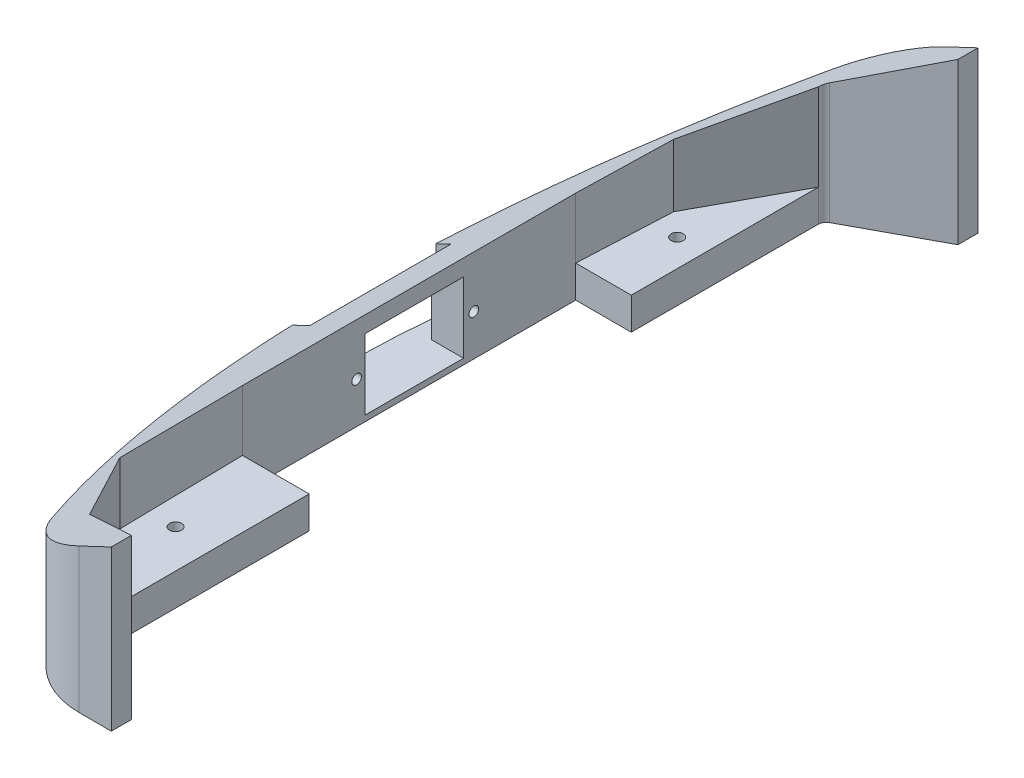
SolidWorks part; units mm, degrees
ref_plane "Front Plane" through (0, 0, 0) normal (0, 0, 1) x (1, 0, 0)
ref_plane "Top Plane" through (0, 0, 0) normal (0, 1, 0) x (1, 0, 0)
ref_plane "Right Plane" through (0, 0, 0) normal (1, 0, 0) x (0, 0, -1)
sketch "front_sketch" plane through (0, 0, 0) normal (0, 1, 0) x (1, 0, 0)
  line L4 (-94.9614, 124.4785) -> (-121.3453, 110.2345)
  line L10 (-122.6787, 107.9994) -> (-122.6787, 48.8108)
  line L24 (-94.9614, 130.8285) -> (-94.9614, 124.4785) construction
  line L25 (-94.9614, 124.4785) -> (-69.5614, 124.4785) construction
  line L28 (-95.6016, -142.8102) -> (-95.6016, -136.4602)
  line L29 (-95.6016, -136.4602) -> (-70.2016, -136.4602) construction
  line L34 (-122.6787, 48.8108) -> (-140.2508, 48.8108)
  line L36 (-140.2508, 48.8108) -> (-140.2508, -56.6452)
  line L43 (-140.2508, -56.6452) -> (-119.167, -56.6452)
  line L44 (-119.167, -56.6452) -> (-119.167, -126.1123)
  line L50 (-119.167, -126.1123) -> (-95.6016, -136.4602)
  line L129 (-94.9614, 130.8285) -> (-69.5614, 130.8285) construction
  line L130 (-94.9614, 130.8285) -> (-69.5614, 130.8285) construction
  line L225 (-95.5505, 130.8285) -> (-157.7358, 130.8285) construction
  line L248 (-94.9614, 130.8285) -> (-95.5505, 130.8285) construction
  line L254 (-94.9614, 130.8285) -> (-95.5505, 130.8285) construction
  line L257 (-94.9614, 130.8285) -> (-105.2412, 130.8285)
  line L258 (-95.5505, 130.8285) -> (-94.9614, 130.8285) construction
  line L259 (-95.6016, -142.8102) -> (-105.7982, -142.8102)
  line L260 (-94.9614, 124.4785) -> (-94.9614, 130.8285)
  line L261 (-94.9614, 130.8285) -> (-95.5505, 130.8285) construction
  line L263 (-95.6016, -142.8102) -> (-70.2016, -142.8102) construction
  line L264 (-95.6016, -142.8102) -> (-70.2016, -142.8102) construction
  line L267 (-97.1554, -142.8102) -> (-95.6016, -142.8102) construction
  line L294 (-94.9614, 130.8285) -> (-95.5505, 130.8285) construction
  line L295 (-157.7358, 130.8285) -> (-157.7358, -142.8102) construction
  line L296 (-157.7358, -142.8102) -> (-97.1554, -142.8102) construction
  line L297 (-95.5505, 130.8285) -> (-157.7358, 130.8285) construction
  arc A41 (-127.9188, 116.8691) -> (-128.5327, -128.7374) centre (116.7138, -6.5464) ccw
  arc A42 (-127.9188, 116.8691) -> (-105.2412, 130.8285) centre (-105.2412, 105.4285) cw
  arc A43 (-128.5327, -128.7374) -> (-105.7982, -142.8102) centre (-105.7982, -117.4102) ccw
  circle A44 centre (-131.2964, 71.9636) radius 1.905
  circle A45 centre (-131.2964, -86.7864) radius 1.905
  arc A48 (-122.6787, 107.9994) -> (-121.3453, 110.2345) centre (-120.1387, 107.9994) cw
  dimension "D12" = 25.4
  dimension "D14" = 25.4
  dimension "D30" = 3.81
  dimension "D4" = 2.54
  dimension "D19" = 6.35
  dimension "D27" = 10.2799
  dimension "D28" = 10.1966
extrude "Boss-Extrude1" add sketch "front_sketch" along normal blind 50.8
sketch "Sketch1" plane through (0, 50.8, 0) normal (0, 1, 0) x (1, 0, 0)
  line L0 (-122.6787, 48.8108) -> (-122.6787, 107.9994)
  line L1 (-122.6787, 107.9994) -> (-138.8333, 78.4051)
  line L2 (-138.8333, 78.4051) -> (-140.2508, 48.8108)
  line L3 (-140.2508, 48.8108) -> (-122.6787, 48.8108)
  line L4 (-119.167, -56.6452) -> (-140.2508, -56.6452)
  line L5 (-119.167, -56.6452) -> (-140.2508, -56.6452) construction
  line L6 (-140.2508, -56.6452) -> (-140.2508, 48.8108) construction
  line L7 (-140.2508, -56.6452) -> (-139.5421, -96.1925)
  line L8 (-139.5421, -96.1925) -> (-119.167, -126.1123)
  line L9 (-119.167, -126.1123) -> (-119.167, -56.6452) construction
  line L10 (-95.6016, -136.4602) -> (-119.167, -126.1123) construction
  line L11 (-119.167, -126.1123) -> (-119.167, -56.6452)
extrude "Cut-Extrude1" cut sketch "Sketch1" against normal blind 40.64
sketch "Sketch3" plane through (0, 0, 142.8102) normal (0, 0, 1) x (1, 0, 0)
  line L0 (-94.9614, 50.8) -> (-157.2871, 21.2708)
  line L1 (-157.2871, 50.8) -> (-157.2871, 0) construction
  line L2 (-157.2871, 21.2708) -> (-157.2871, 50.8)
  line L3 (-157.2871, 50.8) -> (-94.9614, 50.8)
extrude "Cut-Extrude2" cut sketch "Sketch3" against normal through all
sketch "Sketch4" plane through (-140.2508, 0, 0) normal (1, 0, 0) x (0, 0, -1)
  line L0 (-24.4046, 24.1445) -> (20.2563, 24.1445)
  line L1 (-24.4046, 24.1445) -> (-24.4046, 5.0945)
  line L3 (20.2563, 24.1445) -> (20.2563, 5.0945)
  line L4 (-24.4046, 5.0945) -> (-24.4046, 1.8437)
  line L5 (-24.4046, 1.8437) -> (20.2563, 1.8437)
  line L6 (20.2563, 1.8437) -> (20.2563, 5.0945)
  dimension "D1" = 19.05
extrude "Cut-Extrude3" cut sketch "Sketch4" against normal through all
sketch "Sketch6" plane through (-140.2508, 0, 0) normal (1, 0, 0) x (0, 0, -1)
  line L18 (-24.4046, 24.1445) -> (-24.4046, 1.8437) construction
  line L19 (-24.4046, 24.1445) -> (-17.8803, 24.1445)
  line L20 (-24.4046, 24.1445) -> (-24.4046, 1.8437)
  line L21 (-24.4046, 1.8437) -> (-17.8803, 1.8437)
  line L22 (-17.8803, 24.1445) -> (-17.8803, 1.8437)
  line L23 (-24.4046, 1.8437) -> (20.2563, 1.8437) construction
  line L24 (20.2563, 24.1445) -> (-24.4046, 24.1445) construction
  line L25 (20.2563, 1.8437) -> (13.2935, 1.8437)
  line L26 (20.2563, 1.8437) -> (20.2563, 24.1445)
  line L27 (20.2563, 24.1445) -> (13.2935, 24.1445)
  line L28 (13.2935, 1.8437) -> (13.2935, 24.1445)
  circle A1 centre (16.554, 12.9915) radius 1.524
  circle A2 centre (-20.53, 12.9915) radius 1.524
extrude "Boss-Extrude2" add sketch "Sketch6" against normal blind 10.16
